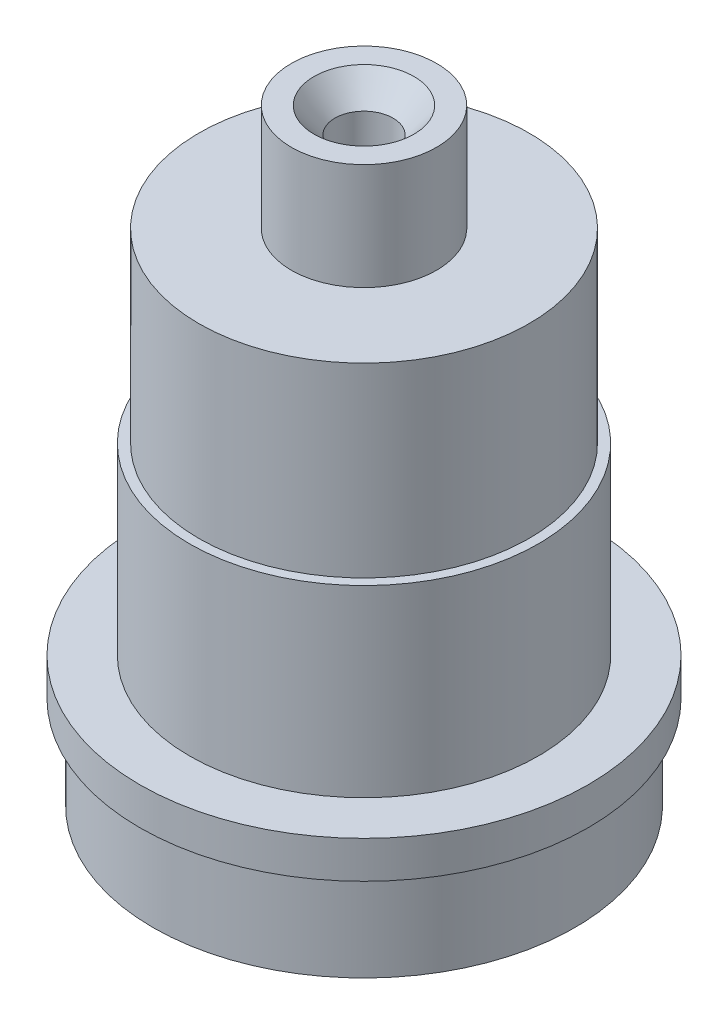
SolidWorks part; units mm, degrees
material "6061-T6 (SS)"
ref_plane "Front Plane" through (0, 0, 0) normal (0, 0, 1) x (1, 0, 0)
ref_plane "Top Plane" through (0, 0, 0) normal (0, 1, 0) x (1, 0, 0)
ref_plane "Right Plane" through (0, 0, 0) normal (1, 0, 0) x (0, 0, -1)
sketch "Sketch1" plane through (0, 0, 0) normal (0, 1, 0) x (1, 0, 0)
  circle A0 centre (0, 0) radius 23.0505
  dimension "D1" = 46.101
extrude "Boss-Extrude1" add sketch "Sketch1" along normal blind 10.16
sketch "Sketch2" plane through (0, 10.16, 0) normal (0, 1, 0) x (1, 0, 0)
  circle A0 centre (0, 0) radius 24.4856
  dimension "D1" = 48.9712
extrude "Boss-Extrude2" add sketch "Sketch2" along normal blind 4.064
sketch "Sketch3" plane through (0, 14.224, 0) normal (0, 1, 0) x (1, 0, 0)
  circle A0 centre (0, 0) radius 19.05
  dimension "D1" = 38.1
extrude "Boss-Extrude3" add sketch "Sketch3" along normal blind 20.066
sketch "Sketch4" plane through (0, 34.29, 0) normal (0, 1, 0) x (1, 0, 0)
  circle A0 centre (0, 0) radius 18.034
  dimension "D1" = 36.068
extrude "Boss-Extrude4" add sketch "Sketch4" along normal blind 20.32
sketch "Sketch5" plane through (0, 54.61, 0) normal (0, 1, 0) x (1, 0, 0)
  circle A0 centre (0, 0) radius 7.9375
  dimension "D1" = 15.875
extrude "Boss-Extrude5" add sketch "Sketch5" along normal blind 11.6332
sketch "Sketch6" plane through (0, 0, 0) normal (0, 0, 1) x (1, 0, 0)
  line L0 (6.35, 66.2432) -> (6.35, 67.7672)
  line L1 (7.9375, 66.2432) -> (-7.9375, 66.2432) construction
  line L2 (6.35, 67.7672) -> (3.3655, 67.7672)
  line L3 (3.3655, 67.7672) -> (3.3655, 71.8312)
  line L4 (3.3655, 71.8312) -> (7.112, 71.8312)
  line L5 (7.112, 71.8312) -> (7.112, 76.1492)
  line L6 (7.112, 76.1492) -> (0, 76.1492)
  line L7 (0, 76.1492) -> (0, 66.2432)
  line L8 (0, 66.2432) -> (6.35, 66.2432)
  dimension "D1" = 6.35
  dimension "D2" = 1.524
  dimension "D3" = 4.064
  dimension "D4" = 4.318
  dimension "D5" = 7.112
  dimension "D6" = 3.3655
revolve "Revolve1" [suppressed] add sketch "Sketch6" angle 360 about L7
fillet "Fillet1" [suppressed] radius 1.27
sketch "Sketch7" plane through (0, 66.2432, 0) normal (0, 1, 0) x (1, 0, 0)
  circle A0 centre (0, 0) radius 3.175
  dimension "D1" = 6.35
extrude "Cut-Extrude1" cut sketch "Sketch7" against normal blind 17.018
chamfer "Chamfer1" distance 2.286 distance2 2.794 1 edges at (0, 66.2432, 3.175) first distance on face at (0, 66.2432, 3.175)
